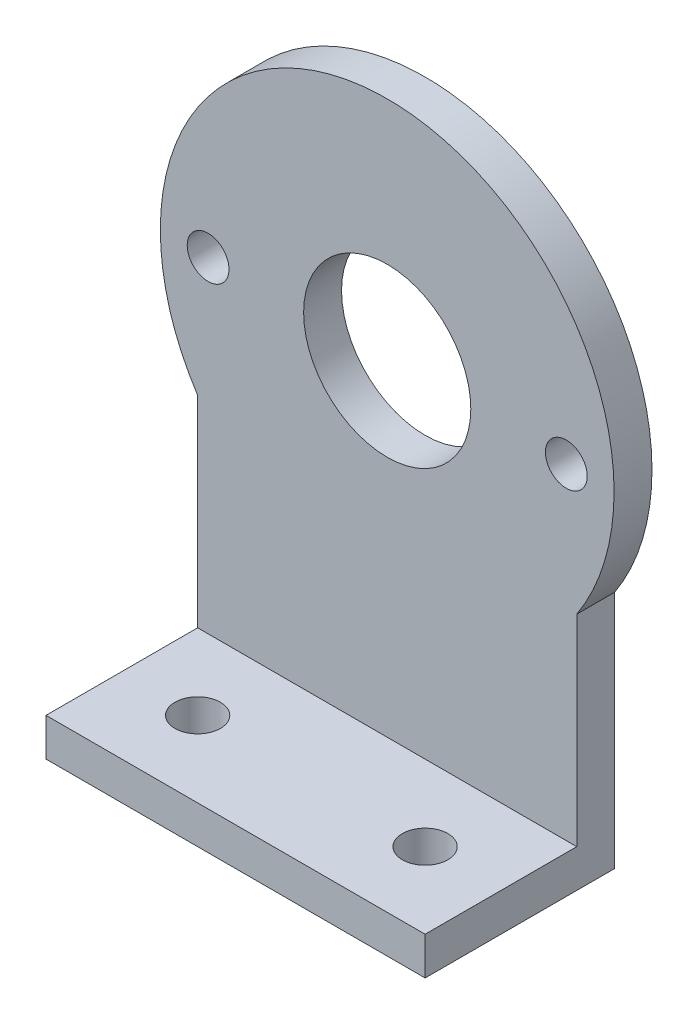
SolidWorks part; units mm, degrees
ref_plane "Front Plane" through (0, 0, 0) normal (0, 0, 1) x (1, 0, 0)
ref_plane "Top Plane" through (0, 0, 0) normal (0, 1, 0) x (1, 0, 0)
ref_plane "Right Plane" through (0, 0, 0) normal (1, 0, 0) x (0, 0, -1)
sketch "Sketch1" plane through (0, 0, 0) normal (0, 0, 1) x (1, 0, 0)
  line L1 (-15.875, -10.4396) -> (15.875, -10.4396)
  line L2 (-15.875, -10.4396) -> (-15.875, -30.48)
  line L3 (-15.875, -30.48) -> (15.875, -30.48)
  line L4 (15.875, -10.4396) -> (15.875, -30.48)
  circle A0 centre (0, 0) radius 19
  arc A2 (-15.875, -10.4396) -> (15.875, -10.4396) centre (0, 0) ccw
  point P6 (-19, 0)
  point P7 (-16.4534, -9.5018)
  dimension "D1" = 38
  dimension "D2" = 30.48
  dimension "D3" = 31.75
extrude "Boss-Extrude1" add sketch "Sketch1" along normal blind 3.175 contours A0 | L2 L1 L4 L3
sketch "Sketch3" plane through (0, 0, 3.175) normal (0, 0, 1) x (1, 0, 0)
  circle A0 centre (0, 0) radius 7
  dimension "D1" = 14
extrude "Cut-Extrude1" cut sketch "Sketch3" against normal through all
sketch "Sketch4" plane through (0, 0, 3.175) normal (0, 0, 1) x (1, 0, 0)
  line L0 (15.875, -10.4396) -> (15.875, -30.48) construction
  line L1 (-15.875, -30.48) -> (15.875, -30.48)
  line L2 (-15.875, -30.48) -> (-15.875, -27.305)
  line L3 (-15.875, -27.305) -> (15.875, -27.305)
  line L4 (15.875, -30.48) -> (15.875, -27.305)
  dimension "D1" = 3.175
extrude "Boss-Extrude2" add sketch "Sketch4" along normal blind 12.7
sketch "Sketch5" plane through (0, -27.305, 0) normal (0, 1, 0) x (1, 0, 0)
  line L0 (-15.875, -9.525) -> (15.875, -9.525) construction
  line L1 (-15.875, -15.875) -> (-15.875, -3.175) construction
  line L2 (15.875, -15.875) -> (15.875, -3.175) construction
  line L3 (0, -3.175) -> (0, -15.875) construction
  line L4 (15.875, -3.175) -> (-15.875, -3.175) construction
  line L5 (15.875, -15.875) -> (-15.875, -15.875) construction
  circle A0 centre (-9.525, -9.525) radius 1.905
  circle A1 centre (9.525, -9.525) radius 1.905
  dimension "D1" = 3.81
  dimension "D2" = 9.525
extrude "Cut-Extrude2" cut sketch "Sketch5" against normal through all
sketch "Sketch6" plane through (0, 0, 3.175) normal (0, 0, 1) x (1, 0, 0)
  line L0 (0, 19) -> (0, -27.305) construction
  line L1 (15.875, -27.305) -> (-15.875, -27.305) construction
  circle A0 centre (0, 0) radius 15 construction
  circle A1 centre (15, 0) radius 1.75
  arc A2 (15.875, -10.4396) -> (-15.875, -10.4396) centre (0, 0) ccw construction
  circle A3 centre (-15, 0) radius 1.75
  dimension "D1" = 30
  dimension "D2" = 3.5
extrude "Cut-Extrude3" cut sketch "Sketch6" against normal through all
